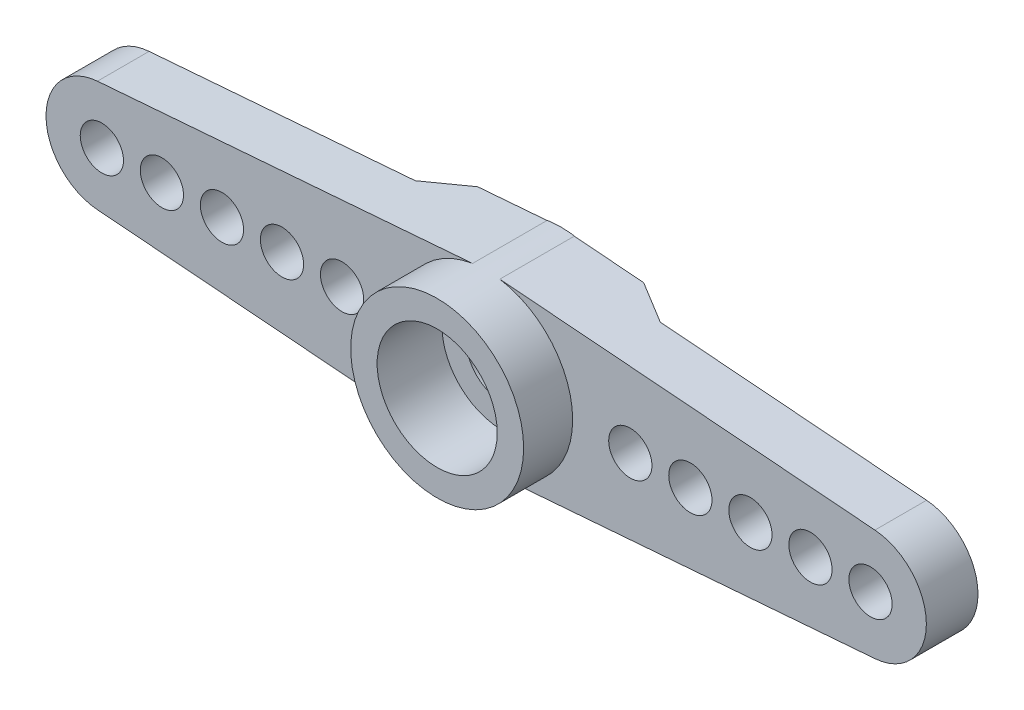
SolidWorks part; units mm, degrees
ref_plane "Plano frontal" through (0, 0, 0) normal (0, 0, 1) x (1, 0, 0)
ref_plane "Plano superior" through (0, 0, 0) normal (0, 1, 0) x (1, 0, 0)
ref_plane "Plano direito" through (0, 0, 0) normal (1, 0, 0) x (0, 0, -1)
sketch "Esboço1" plane through (0, 0, 0) normal (0, 0, 1) x (1, 0, 0)
  circle A0 centre (0, 0) radius 2.45
  circle A1 centre (0, 0) radius 3.6
  dimension "D1" = 7.2
  dimension "D2" = 4.9
extrude "Ressalto-extrusão1" add sketch "Esboço1" along normal blind 2.8 and the other way blind 0.15
sketch "Esboço2" plane through (0, 0, -0.15) normal (0, 0, -1) x (-1, 0, 0)
  circle A0 centre (0, 0) radius 2.5
  circle A1 centre (0, 0) radius 1
  dimension "D1" = 2
extrude "Ressalto-extrusão2" add sketch "Esboço2" along normal blind 0.5 separate body
sketch "Esboço3" plane through (0, 0, -0.15) normal (0, 0, -1) x (-1, 0, 0)
  circle A0 centre (0, 0) radius 3.6
  circle A1 centre (0, 0) radius 2.45
  dimension "D1" = 7.2
  dimension "D2" = 4.9
extrude "Ressalto-extrusão3" add sketch "Esboço3" along normal blind 2.2
sketch "Esboço4" plane through (0, 0, 0) normal (0, 1, 0) x (1, 0, 0)
  line L0 (3.6, 2.35) -> (-3.6, 2.35) construction
  line L1 (-18.325, 1.39) -> (3.675, 1.39)
  line L2 (-18.325, 1.39) -> (-18.325, -0.76)
  line L3 (3.675, 1.39) -> (3.675, -5.4692) construction
  line L5 (3.675, -0.76) -> (-18.325, -0.76)
  line L6 (3.675, 1.39) -> (3.675, -0.76)
  point P0 (0, 0)
  dimension "D1" = 0.96
  dimension "D2" = 22
extrude "Ressalto-extrusão4" add sketch "Esboço4" along normal mid plane 7.2
sketch "Esboço5" plane through (0, 0, 0.76) normal (0, 0, 1) x (1, 0, 0)
  line L0 (0, 0) -> (-16, 0) construction
  line L1 (-16, 0) -> (-16, -7.6538) construction
  line L3 (-16.75, 0) -> (-18.05, 0) construction
  line L4 (-0.5669, -3.5551) -> (-16.1836, -2.3177)
  line L5 (-0.5669, 3.5551) -> (-16.1836, 2.3177)
  line L6 (5.6455, 5.6158) -> (5.6455, -6.5456)
  line L15 (-22.4536, -6.5456) -> (5.6455, -6.5456)
  line L16 (-22.4536, 5.6158) -> (-22.4536, -6.5456)
  line L17 (5.6455, 5.6158) -> (-22.4536, 5.6158)
  circle A0 centre (-16, 0) radius 0.75
  arc A1 (-16.1836, 2.3177) -> (-16.1836, -2.3177) centre (-16, 0) ccw
  arc A2 (-0.5669, -3.5551) -> (-0.5669, 3.5551) centre (0, 0) ccw
  line M27 (3.675, 3.6) -> (0, 3.6)
  arc M28 (0, 3.6) -> (0, -3.6) centre (0, 0) cw
  line M29 (0, -3.6) -> (3.675, -3.6)
  dimension "D2" = 1.5
  dimension "D4" = 4.65
  dimension "D1" = 16
  dimension "D3" = 1.3
extrude "Corte-extrusão2" cut sketch "Esboço5" against normal blind 7.2 contours L17 L16 L15 | M27 M28 M29 region at (5.3393, -0.4649, 0.76)
sketch "Esboço7" plane through (0, 0, 2.8) normal (0, 0, 1) x (1, 0, 0)
  circle A0 centre (0, 0) radius 2.5
extrude "Corte-extrusão3" cut sketch "Esboço7" against normal blind 2.7
sketch "Esboço8" plane through (0, 0, 0.1) normal (0, 0, 1) x (1, 0, 0)
  line L0 (0, 0) -> (-16, 0) construction
  line L1 (-6, 0) -> (-6, -4.249) construction
  line L3 (-8.5, -4.249) -> (-8.5, 0) construction
  line L5 (-11, 0) -> (-11, -4.249) construction
  line L9 (-13.5, 0) -> (-13.5, -4.249) construction
  line L15 (-16, -4.249) -> (-16, 0) construction
  circle A0 centre (0, 0) radius 1.5
  circle A1 centre (-6, 0) radius 0.9
  circle A2 centre (-8.5, 0) radius 0.9
  circle A3 centre (-11, 0) radius 0.9
  circle A4 centre (-13.5, 0) radius 0.9
  circle A5 centre (-16, 0) radius 0.9
  dimension "D1" = 3
  dimension "D7" = 1.8
  dimension "D8" = 1.8
  dimension "D9" = 1.8
  dimension "D10" = 1.8
  dimension "D11" = 1.8
  dimension "D2" = 6
  dimension "D3" = 8.5
  dimension "D4" = 11
  dimension "D5" = 13.5
  dimension "D6" = 16
extrude "Corte-extrusão4" cut sketch "Esboço8" against normal mid plane 13.8
sketch "Esboço10" plane through (0, 0, -1.39) normal (0, 0, -1) x (-1, 0, 0)
  line L0 (5.1, -3.1959) -> (5.1, -2.3959) construction
  line L1 (18.325, 0) -> (3.6, 0) construction
  line L3 (5.1, 3.1959) -> (5.1, 2.3959) construction
  line L4 (5.1, -3.1959) -> (5.1, -2.3959)
  line L5 (5.1, -2.3959) -> (2.6869, -2.3959)
  line L6 (5.1938, -0.4) -> (3.5777, -0.4)
  line L7 (5.1938, 0.4) -> (3.5777, 0.4)
  line L8 (5.1, -3.1959) -> (0, -3.6)
  line L9 (5.1, 3.1959) -> (0, 3.6)
  line L10 (5.1, 2.3959) -> (2.6869, 2.3959)
  line L11 (5.1, 3.1959) -> (5.1, 2.3959)
  line L13 (5.1, 2.3959) -> (5.1, 3.1959) construction
  arc A0 (16.1836, -2.3177) -> (16.1836, 2.3177) centre (16, 0) ccw construction
  arc A1 (3.5777, -0.4) -> (3.5777, 0.4) centre (0, 0) ccw
  arc A2 (0, -3.6) -> (2.6869, -2.3959) centre (0, 0) ccw
  arc A3 (2.6869, 2.3959) -> (0, 3.6) centre (0, 0) ccw
  arc A4 (5.1938, 0.4) -> (5.1938, -0.4) centre (6, 0) ccw
  circle M6 centre (6, 0) radius 0.9
  line M10 (16.1836, 2.3177) -> (0.5669, 3.5551)
  arc M11 (0.5669, 3.5551) -> (0.5669, -3.5551) centre (0, 0) cw
  line M12 (0.5669, -3.5551) -> (16.1836, -2.3177)
  dimension "D1" = 0.8
  dimension "D2" = 0.4
  dimension "D3" = 0.4
extrude "Ressalto-extrusão5" add sketch "Esboço10" along normal blind 0.95 contours L4 L5 M11 M12 | L7 L6 M6 M11 | L11 L10 M10 M11 region at (-3.4237, -2.9192, -1.39) region at (-3.4237, 2.9192, -1.39) region at (-4.3618, 0, -1.39)
sketch "Esboço11" plane through (0, 0, 0) normal (0, 1, 0) x (1, 0, 0)
  line L0 (-5.1, 1.39) -> (-2.0456, 3.1535)
  line L2 (-5.1, 1.39) -> (-5.859, 1.39)
  line L3 (-5.1, 1.39) -> (-16.1836, 1.39) construction
  line L4 (-5.859, 1.39) -> (-5.859, 3.1535)
  line L5 (-5.859, 3.1535) -> (-2.0456, 3.1535)
extrude "Corte-extrusão5" cut sketch "Esboço11" against normal blind 4.95 and the other way blind 12
sketch3d "3DSketch1"
  line L0 (0, -3.9567, -2.35) -> (0, 4.5741, -2.35)
  line L1 (0, -3.9567, -2.35) -> (0, -3.9567, -0.1994)
  line L2 (0, -3.9567, -0.1994) -> (0, 4.5741, -0.1994)
  line L3 (0, 4.5741, -0.1994) -> (0, 4.5741, -2.35)
ref_plane "Plano1" through (0, 0, 0) normal (-1, 0, 0) x (0, 0, 1)
mirror "Espelhar20" about plane through (0, 0, 0) normal (-1, 0, 0) of bodies 116
